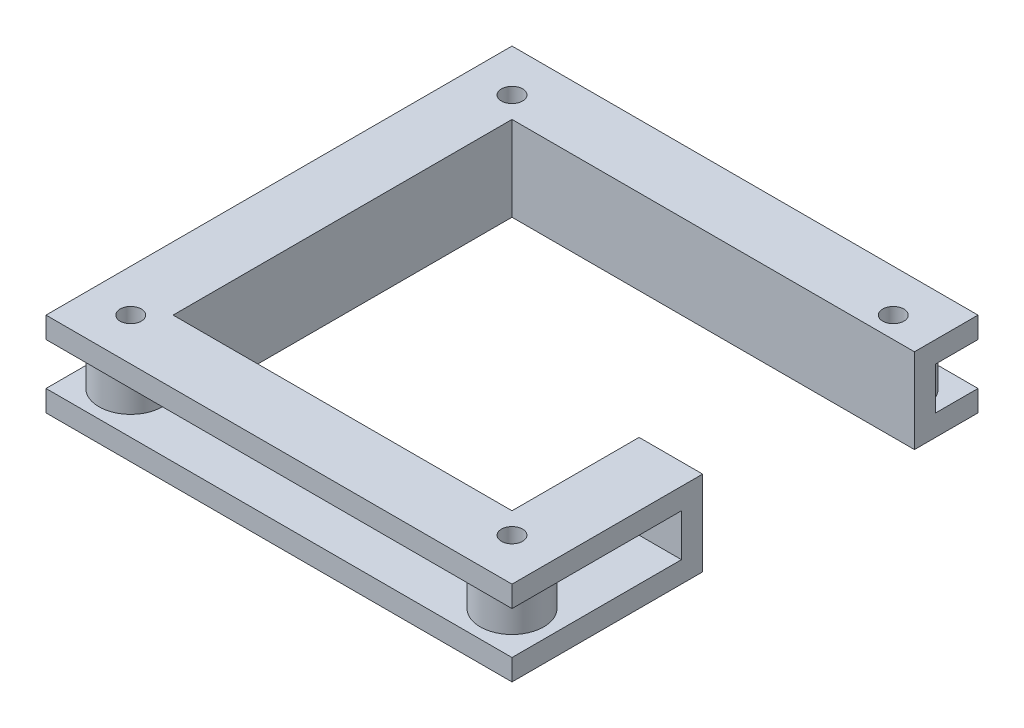
SolidWorks part; units mm, degrees
ref_plane "Front Plane" through (0, 0, 0) normal (0, 0, 1) x (1, 0, 0)
ref_plane "Top Plane" through (0, 0, 0) normal (0, 1, 0) x (1, 0, 0)
ref_plane "Right Plane" through (0, 0, 0) normal (1, 0, 0) x (0, 0, -1)
sketch "Sketch1" plane through (0, 0, 0) normal (0, 1, 0) x (1, 0, 0)
  line L0 (200, -20) -> (200, 200)
  line L1 (0, 0) -> (180, 0)
  line L2 (0, 0) -> (0, 180)
  line L3 (0, 180) -> (180, 180)
  line L4 (180, 0) -> (180, 180)
  line L5 (-20, 200) -> (200, 200)
  line L6 (-20, -20) -> (-20, 200)
  line L7 (-20, -20) -> (200, -20)
  line L8 (170, 10) -> (170, 170)
  line L9 (10, 170) -> (170, 170)
  line L10 (10, 10) -> (10, 170)
  line L11 (10, 10) -> (170, 10)
  line L12 (90, 200) -> (90, -20) construction
  line L13 (-20, 90) -> (200, 90) construction
  circle A0 centre (0, 180) radius 5
  circle A1 centre (180, 180) radius 5
  circle A2 centre (180, 0) radius 5
  circle A3 centre (0, 0) radius 5
  dimension "D5" = 10
  dimension "D1" = 180
  dimension "D2" = 180
  dimension "D3" = 20
  dimension "D4" = 10
extrude "Boss-Extrude1" add sketch "Sketch1" along normal blind 40 contours L2 A3 L1 A2 L4 A1 L3 A0 L11 L10 L9 L8 | L6 L7 L0 L5 L1 A3 L2 A0 L3 A1 L4 A2 region at (90, 0, 16.8887) region at (5.3355, 0, -5.3355)
sketch "Sketch4" plane through (0, 40, 0) normal (0, 1, 0) x (1, 0, 0)
  line L0 (170, 170) -> (200, 170) construction
  line L1 (200, -20) -> (200, 200) construction
  line L2 (170, 70) -> (200, 70) construction
  line L4 (170, 170) -> (200, 170)
  line L5 (170, 170) -> (170, 70)
  line L6 (170, 70) -> (200, 70)
  line L7 (200, 170) -> (200, 70)
  dimension "D1" = 100
extrude "Cut-Extrude1" cut sketch "Sketch4" against normal through all
shell "Shell1" thickness 10 removed face at (200, 20, -185) removed face at (200, 20, -25) removed face at (90, 20, 20) removed face at (-20, 20, -90) removed face at (90, 20, -200)
